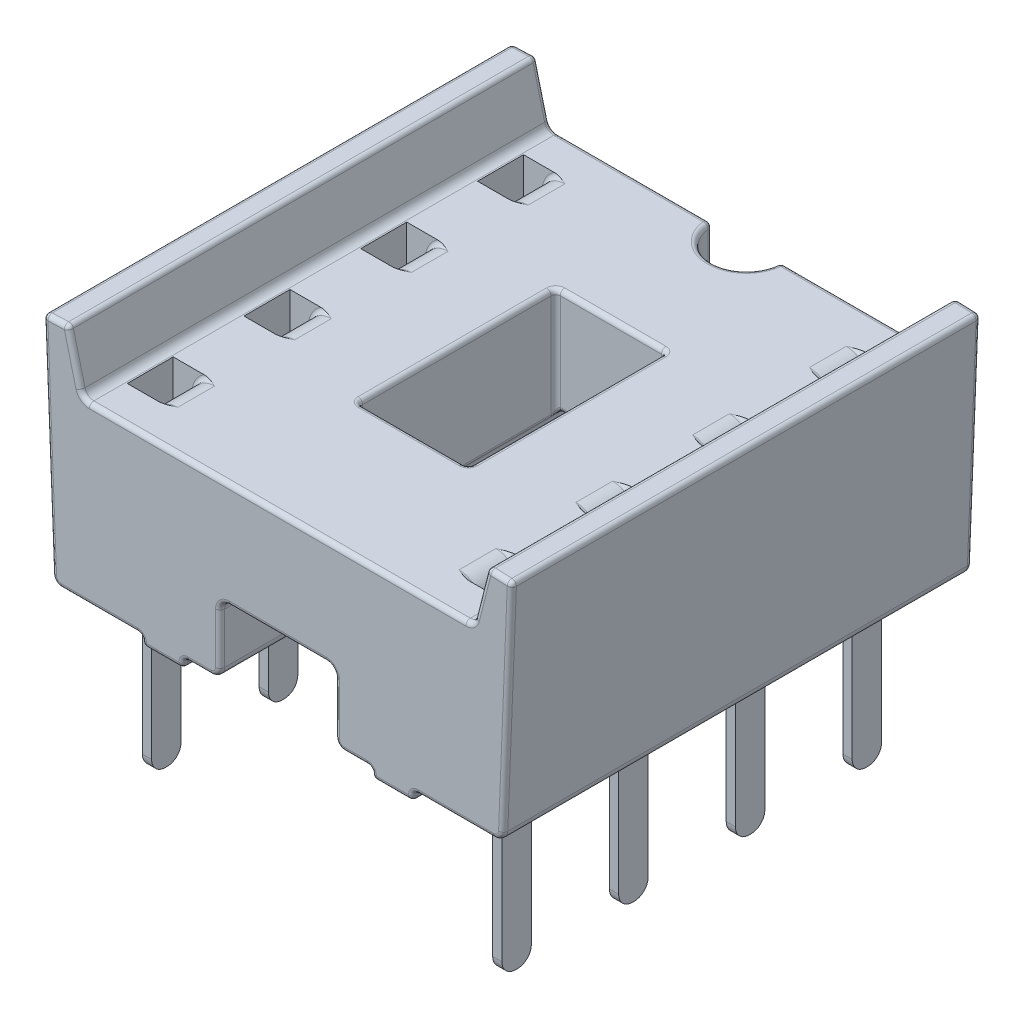
SolidWorks part; units mm, degrees
material "ABS"
ref_plane "Front Plane" through (0, 0, 0) normal (0, 0, 1) x (1, 0, 0)
ref_plane "Top Plane" through (0, 0, 0) normal (0, 1, 0) x (1, 0, 0)
ref_plane "Right Plane" through (0, 0, 0) normal (1, 0, 0) x (0, 0, -1)
sketch "Sketch1" plane through (0, 0, 0) normal (0, 0, 1) x (1, 0, 0)
  line L0 (-2.05, 0) -> (2.05, 0) construction
  line L1 (2.05, 0) -> (2.95, 0)
  line L2 (-2.05, 0) -> (-2.95, 0)
  line L3 (2.95, 0) -> (2.95, 0.2)
  line L4 (2.95, 0.2) -> (4.9, 0.2)
  line L5 (-2.95, 0) -> (-2.95, 0.2)
  line L6 (-2.95, 0.2) -> (-4.9, 0.2)
  line L7 (-2.05, 0) -> (-2.05, 0.2)
  line L8 (-2.05, 0.2) -> (-2.95, 0.2) construction
  line L9 (2.05, 0) -> (2.05, 0.2)
  line L10 (2.05, 0.2) -> (2.95, 0.2) construction
  line L11 (0, 0) -> (0, 1.7) construction
  line L12 (-1.25, 1.7) -> (1.25, 1.7)
  line L13 (-1.25, 1.7) -> (-1.25, 0.2)
  line L14 (-1.25, 0.2) -> (-2.05, 0.2)
  line L15 (1.25, 1.7) -> (1.25, 0.2)
  line L16 (1.25, 0.2) -> (2.05, 0.2)
  line L17 (-5.1, 5.2) -> (-4.5604, 5.2216)
  line L18 (-5.1, 5.2) -> (-5.1, 0.2) construction
  line L19 (-5.1, 0.2) -> (-4.9, 0.2) construction
  line L20 (4.9, 0.2) -> (5.1, 0.2) construction
  line L21 (-5.1, 5.2) -> (-4.9, 0.2)
  line L22 (4.9, 0.2) -> (5.1, 5.2)
  line L23 (5.1, 5.2) -> (5.1, 0.2) construction
  line L24 (5.1, 5.2) -> (4.5604, 5.2216)
  line L25 (0, 1.7) -> (0, 4) construction
  line L26 (-4.25, 4) -> (4.25, 4)
  line L27 (-4.5604, 5.2216) -> (-4.25, 4)
  line L28 (4.5604, 5.2216) -> (4.25, 4)
  dimension "D1" = 4.1
  dimension "D2" = 9.8
  dimension "D3" = 0.9
  dimension "D4" = 2.5
  dimension "D5" = 1.5
  dimension "D6" = 0.2
  dimension "D7" = 10.2
  dimension "D8" = 5
  dimension "D9" = 0.54
  dimension "D10" = 4
  dimension "D11" = 8.5
extrude "Boss-Extrude1" add sketch "Sketch1" along normal mid plane 10.2
fillet "Fillet5" radius 0.2 8 edges at (1.25, 0.2, 0) (4.9, 0.2, 0) (-4.9, 0.2, 0) (-1.25, 0.2, 0) (-1.25, 1.7, 0) (1.25, 1.7, 0) (4.25, 4, 0) (-4.25, 4, 0)
sketch "Sketch2" plane through (0, 4, 0) normal (0, 1, 0) x (1, 0, 0)
  line L1 (0, 0) -> (0, 5.1) construction
  line L2 (-1.2, 2.15) -> (1.2, 2.15)
  line L3 (-1.2, 2.15) -> (-1.2, -2.15)
  line L4 (-1.2, -2.15) -> (1.2, -2.15)
  line L5 (1.2, 2.15) -> (1.2, -2.15)
  line L6 (-1.2, 2.15) -> (1.2, -2.15) construction
  line L7 (-1.2, -2.15) -> (1.2, 2.15) construction
  line L8 (4.0945, 5.1) -> (-4.0945, 5.1) construction
  circle A0 centre (0, 5.1) radius 0.75
  point P2 (0, 0)
  dimension "D1" = 1.5
  dimension "D2" = 4.3
  dimension "D3" = 2.4
extrude "Cut-Extrude1" cut sketch "Sketch2" against normal up to surface (4 mm away) up to face at (-2.5, 0, 0)
sketch "Sketch3" plane through (0, 4, 0) normal (0, 1, 0) x (1, 0, 0)
  line L0 (0, 1.27) -> (0, -1.27) construction
  line L1 (0, 1.27) -> (0, 3.81) construction
  line L2 (0, -1.27) -> (0, -3.81) construction
  line L3 (-3.81, 1.27) -> (3.81, 1.27) construction
  line L4 (3.81, -1.27) -> (-3.81, -1.27) construction
  line L5 (-3.81, -3.81) -> (3.81, -3.81) construction
  line L6 (-3.81, 3.81) -> (3.81, 3.81) construction
  line L8 (-4.06, 4.31) -> (-3.56, 4.31)
  line L9 (-4.06, 4.31) -> (-4.06, 3.31)
  line L10 (-4.06, 3.31) -> (-3.56, 3.31)
  line L11 (-3.56, 4.31) -> (-3.56, 3.31)
  line L12 (-4.06, 4.31) -> (-3.56, 3.31) construction
  line L13 (-4.06, 3.31) -> (-3.56, 4.31) construction
  line L14 (-4.06, 1.77) -> (-3.56, 1.77)
  line L15 (-4.06, 1.77) -> (-4.06, 0.77)
  line L16 (-4.06, 0.77) -> (-3.56, 0.77)
  line L17 (-3.56, 1.77) -> (-3.56, 0.77)
  line L18 (-4.06, 1.77) -> (-3.56, 0.77) construction
  line L19 (-4.06, 0.77) -> (-3.56, 1.77) construction
  line L20 (-4.06, -0.77) -> (-3.56, -0.77)
  line L21 (-4.06, -0.77) -> (-4.06, -1.77)
  line L22 (-4.06, -1.77) -> (-3.56, -1.77)
  line L23 (-3.56, -0.77) -> (-3.56, -1.77)
  line L24 (-4.06, -0.77) -> (-3.56, -1.77) construction
  line L25 (-4.06, -1.77) -> (-3.56, -0.77) construction
  line L26 (-4.06, -3.31) -> (-3.56, -3.31)
  line L27 (-4.06, -3.31) -> (-4.06, -4.31)
  line L28 (-4.06, -4.31) -> (-3.56, -4.31)
  line L29 (-3.56, -3.31) -> (-3.56, -4.31)
  line L30 (-4.06, -3.31) -> (-3.56, -4.31) construction
  line L31 (-4.06, -4.31) -> (-3.56, -3.31) construction
  line L32 (4.06, -3.31) -> (3.56, -3.31)
  line L33 (4.06, -3.31) -> (4.06, -4.31)
  line L34 (4.06, -4.31) -> (3.56, -4.31)
  line L35 (3.56, -3.31) -> (3.56, -4.31)
  line L36 (4.06, -3.31) -> (3.56, -4.31) construction
  line L37 (4.06, -4.31) -> (3.56, -3.31) construction
  line L38 (4.06, -0.77) -> (3.56, -0.77)
  line L39 (4.06, -0.77) -> (4.06, -1.77)
  line L40 (4.06, -1.77) -> (3.56, -1.77)
  line L41 (3.56, -0.77) -> (3.56, -1.77)
  line L42 (4.06, -0.77) -> (3.56, -1.77) construction
  line L43 (4.06, -1.77) -> (3.56, -0.77) construction
  line L44 (4.06, 1.77) -> (3.56, 1.77)
  line L45 (4.06, 1.77) -> (4.06, 0.77)
  line L46 (4.06, 0.77) -> (3.56, 0.77)
  line L47 (3.56, 1.77) -> (3.56, 0.77)
  line L48 (4.06, 1.77) -> (3.56, 0.77) construction
  line L49 (4.06, 0.77) -> (3.56, 1.77) construction
  line L50 (4.06, 4.31) -> (3.56, 4.31)
  line L51 (4.06, 4.31) -> (4.06, 3.31)
  line L52 (4.06, 3.31) -> (3.56, 3.31)
  line L53 (3.56, 4.31) -> (3.56, 3.31)
  line L54 (4.06, 4.31) -> (3.56, 3.31) construction
  line L55 (4.06, 3.31) -> (3.56, 4.31) construction
  dimension "D1" = 2.54
  dimension "D2" = 7.62
  dimension "D3" = 0.5
  dimension "D4" = 1
extrude "Cut-Extrude2" cut sketch "Sketch3" against normal blind 3
fillet "Fillet6" radius 0.1 12 edges at (-1.2, 2.8161, 2.15) (1.2, 2.8161, 2.15) (1.2, 2.8161, -2.15) (-1.2, 2.8161, -2.15) (-2.95, 0, 0) (-2.05, 0, 0) (2.05, 0, 0) (2.95, 0, 0) (5.1, 5.2, 0) (4.5604, 5.2216, 0) (-5.1, 5.2, 0) (-4.5604, 5.2216, 0)
fillet "Fillet7" radius 0.5 8 edges at (3.56, 4, -3.81) (3.56, 4, -1.27) (3.56, 4, 1.27) (3.56, 4, 3.81) (-3.56, 4, 3.81) (-3.56, 4, 1.27) (-3.56, 4, -1.27) (-3.56, 4, -3.81)
fillet "Fillet8" radius 0.1 6 edges at (2.95, 0.2, 0) (2.05, 0.2, 0) (-2.05, 0.2, 0) (-2.95, 0.2, 0) (-0.75, 2.85, -5.1) (0.75, 2.85, -5.1)
fillet "Fillet10" radius 0.1 132 edges at (3.56, 2.25, 4.31) (3.56, 2.25, 3.31) (3.56, 2.25, 1.77) (3.56, 2.25, 0.77) (3.56, 2.25, -0.77) (3.56, 2.25, -1.77) (3.56, 2.25, -3.31) (3.56, 2.25, -4.31) (-3.56, 2.25, -4.31) (-3.56, 2.25, -3.31) (-3.56, 2.25, -0.77) (-3.56, 2.25, -1.77) (-3.56, 2.25, 0.77) (-3.56, 2.25, 1.77) (-3.56, 2.25, 4.31) (-3.56, 2.25, 3.31) (1.0752, 1.6984, -2.15) (1.1867, 1.646, -2.0999) (1.2, 1.6323, 0) (1.1844, 1.6481, 2.1037) (1.0752, 1.6984, 2.15) (0, 1.7, 2.15) (-1.0752, 1.6984, 2.15) (-1.1867, 1.646, 2.0999) (-1.2, 1.6323, 0) (-1.1844, 1.6481, -2.1037) (-1.0752, 1.6984, -2.15) (-1.1707, 4, -2.1207) (0, 4, -2.15) (1.1707, 4, -2.1207) (1.2, 4, 0) (1.1707, 4, 2.1207) (0, 4, 2.15) (-1.1707, 4, 2.1207) (4.2172, 4.0421, 5.1) (4.4144, 4.6469, 5.1) (4.5776, 5.1986, 5.1) (4.8207, 5.2112, 5.1) (5.0696, 5.1719, 5.1) (5.0018, 2.746, 5.1) (4.8464, 0.2558, 5.1) (3.8789, 0.2, 5.1) (2.9793, 0.1707, 5.1) (2.9207, 0.0293, 5.1) (2.5, 0, 5.1) (2.0793, 0.0293, 5.1) (2.0207, 0.1707, 5.1) (1.7, 0.2, 5.1) (1.3086, 0.2586, 5.1) (1.25, 0.95, 5.1) (1.1914, 1.6414, 5.1) (0, 1.7, 5.1) (-1.1914, 1.6414, 5.1) (-1.25, 0.95, 5.1) (-1.3086, 0.2586, 5.1) (-1.7, 0.2, 5.1) (-2.0207, 0.1707, 5.1) (-2.0793, 0.0293, 5.1) (-2.5, 0, 5.1) (-2.9207, 0.0293, 5.1) (-2.9793, 0.1707, 5.1) (-3.8789, 0.2, 5.1) (-4.8464, 0.2558, 5.1) (-5.0018, 2.746, 5.1) (-5.0696, 5.1719, 5.1) (-4.8207, 5.2112, 5.1) (-4.5776, 5.1986, 5.1) (-4.4144, 4.6469, 5.1) (-4.2172, 4.0421, 5.1) (4.2172, 4.0421, -5.1) (4.4144, 4.6469, -5.1) (4.5776, 5.1986, -5.1) (4.8207, 5.2112, -5.1) (5.0696, 5.1719, -5.1) (5.0018, 2.746, -5.1) (4.8464, 0.2558, -5.1) (3.8789, 0.2, -5.1) (2.9793, 0.1707, -5.1) (2.9207, 0.0293, -5.1) (2.5, 0, -5.1) (2.0793, 0.0293, -5.1) (2.0207, 0.1707, -5.1) (1.7, 0.2, -5.1) (1.3086, 0.2586, -5.1) (1.25, 0.95, -5.1) (1.1914, 1.6414, -5.1) (0.947, 1.7, -5.1) (0.7777, 1.7, -5.0748) (0, 1.7, -4.35) (-0.7777, 1.7, -5.0748) (-0.947, 1.7, -5.1) (-1.1914, 1.6414, -5.1) (-1.25, 0.95, -5.1) (-1.3086, 0.2586, -5.1) (-1.7, 0.2, -5.1) (-2.0207, 0.1707, -5.1) (-2.0793, 0.0293, -5.1) (-2.5, 0, -5.1) (-2.9207, 0.0293, -5.1) (-2.9793, 0.1707, -5.1) (-3.8789, 0.2, -5.1) (-4.8464, 0.2558, -5.1) (-5.0018, 2.746, -5.1) (-5.0696, 5.1719, -5.1) (-4.8207, 5.2112, -5.1) (-4.5776, 5.1986, -5.1) (-4.4144, 4.6469, -5.1) (-4.2172, 4.0421, -5.1) (-2.4693, 4, -5.1) (-0.7777, 4, -5.0748) (0, 4, -4.35) (0.7777, 4, -5.0748) (3.4136, 3.8536, 4.31) (3.4136, 3.8536, 3.31) (3.4136, 3.8536, 1.77) (3.4136, 3.8536, 0.77) (3.4136, 3.8536, -0.77) (3.4136, 3.8536, -1.77) (3.4136, 3.8536, -3.31) (3.4136, 3.8536, -4.31) (-3.4136, 3.8536, -4.31) (-3.4136, 3.8536, -3.31) (-3.4136, 3.8536, -0.77) (-3.4136, 3.8536, -1.77) (-3.4136, 3.8536, 0.77) (-3.4136, 3.8536, 1.77) (-3.4136, 3.8536, 4.31) (-3.4136, 3.8536, 3.31) (0, 1.7, -2.15) (-1.2, 4, 0) (0, 4, 5.1) (2.4693, 4, -5.1)
sketch "Sketch4" plane through (0, 0.2, 0) normal (0, -1, 0) x (1, 0, 0)
  line L0 (0, 1.27) -> (0, -1.27) construction
  line L1 (0, 1.27) -> (0, 3.81) construction
  line L2 (0, -1.27) -> (0, -3.81) construction
  line L3 (-3.81, 1.27) -> (3.81, 1.27) construction
  line L4 (-3.81, -1.27) -> (3.81, -1.27) construction
  line L5 (-3.81, 3.81) -> (3.81, 3.81) construction
  line L6 (-3.81, -3.81) -> (3.81, -3.81) construction
  line L8 (3.71, 4.13) -> (3.91, 4.13)
  line L9 (3.71, 4.13) -> (3.71, 3.49)
  line L10 (3.71, 3.49) -> (3.91, 3.49)
  line L11 (3.91, 4.13) -> (3.91, 3.49)
  line L12 (3.71, 4.13) -> (3.91, 3.49) construction
  line L13 (3.71, 3.49) -> (3.91, 4.13) construction
  line L14 (3.71, 1.59) -> (3.91, 1.59)
  line L15 (3.71, 1.59) -> (3.71, 0.95)
  line L16 (3.71, 0.95) -> (3.91, 0.95)
  line L17 (3.91, 1.59) -> (3.91, 0.95)
  line L18 (3.71, 1.59) -> (3.91, 0.95) construction
  line L19 (3.71, 0.95) -> (3.91, 1.59) construction
  line L20 (3.71, -0.95) -> (3.91, -0.95)
  line L21 (3.71, -0.95) -> (3.71, -1.59)
  line L22 (3.71, -1.59) -> (3.91, -1.59)
  line L23 (3.91, -0.95) -> (3.91, -1.59)
  line L24 (3.71, -0.95) -> (3.91, -1.59) construction
  line L25 (3.71, -1.59) -> (3.91, -0.95) construction
  line L26 (3.71, -3.49) -> (3.91, -3.49)
  line L27 (3.71, -3.49) -> (3.71, -4.13)
  line L28 (3.71, -4.13) -> (3.91, -4.13)
  line L29 (3.91, -3.49) -> (3.91, -4.13)
  line L30 (3.71, -3.49) -> (3.91, -4.13) construction
  line L31 (3.71, -4.13) -> (3.91, -3.49) construction
  line L32 (-3.71, 4.13) -> (-3.91, 4.13)
  line L33 (-3.71, 4.13) -> (-3.71, 3.49)
  line L34 (-3.71, 3.49) -> (-3.91, 3.49)
  line L35 (-3.91, 4.13) -> (-3.91, 3.49)
  line L36 (-3.71, 4.13) -> (-3.91, 3.49) construction
  line L37 (-3.71, 3.49) -> (-3.91, 4.13) construction
  line L38 (-3.71, 1.59) -> (-3.91, 1.59)
  line L39 (-3.71, 1.59) -> (-3.71, 0.95)
  line L40 (-3.71, 0.95) -> (-3.91, 0.95)
  line L41 (-3.91, 1.59) -> (-3.91, 0.95)
  line L42 (-3.71, 1.59) -> (-3.91, 0.95) construction
  line L43 (-3.71, 0.95) -> (-3.91, 1.59) construction
  line L44 (-3.71, -0.95) -> (-3.91, -0.95)
  line L45 (-3.71, -0.95) -> (-3.71, -1.59)
  line L46 (-3.71, -1.59) -> (-3.91, -1.59)
  line L47 (-3.91, -0.95) -> (-3.91, -1.59)
  line L48 (-3.71, -0.95) -> (-3.91, -1.59) construction
  line L49 (-3.71, -1.59) -> (-3.91, -0.95) construction
  line L50 (-3.71, -3.49) -> (-3.91, -3.49)
  line L51 (-3.71, -3.49) -> (-3.71, -4.13)
  line L52 (-3.71, -4.13) -> (-3.91, -4.13)
  line L53 (-3.91, -3.49) -> (-3.91, -4.13)
  line L54 (-3.71, -3.49) -> (-3.91, -4.13) construction
  line L55 (-3.71, -4.13) -> (-3.91, -3.49) construction
  dimension "D1" = 2.54
  dimension "D2" = 0.2
  dimension "D3" = 0.64
  dimension "D4" = 7.62
extrude "Boss-Extrude2" add sketch "Sketch4" along normal blind 3.5
fillet "Fillet11" radius 0.3 16 edges at (3.81, -3.3, 4.13) (3.81, -3.3, 3.49) (3.81, -3.3, 1.59) (3.81, -3.3, 0.95) (3.81, -3.3, -0.95) (3.81, -3.3, -1.59) (3.81, -3.3, -3.49) (3.81, -3.3, -4.13) (-3.81, -3.3, -4.13) (-3.81, -3.3, -3.49) (-3.81, -3.3, -1.59) (-3.81, -3.3, -0.95) (-3.81, -3.3, 0.95) (-3.81, -3.3, 1.59) (-3.81, -3.3, 3.49) (-3.81, -3.3, 4.13)
